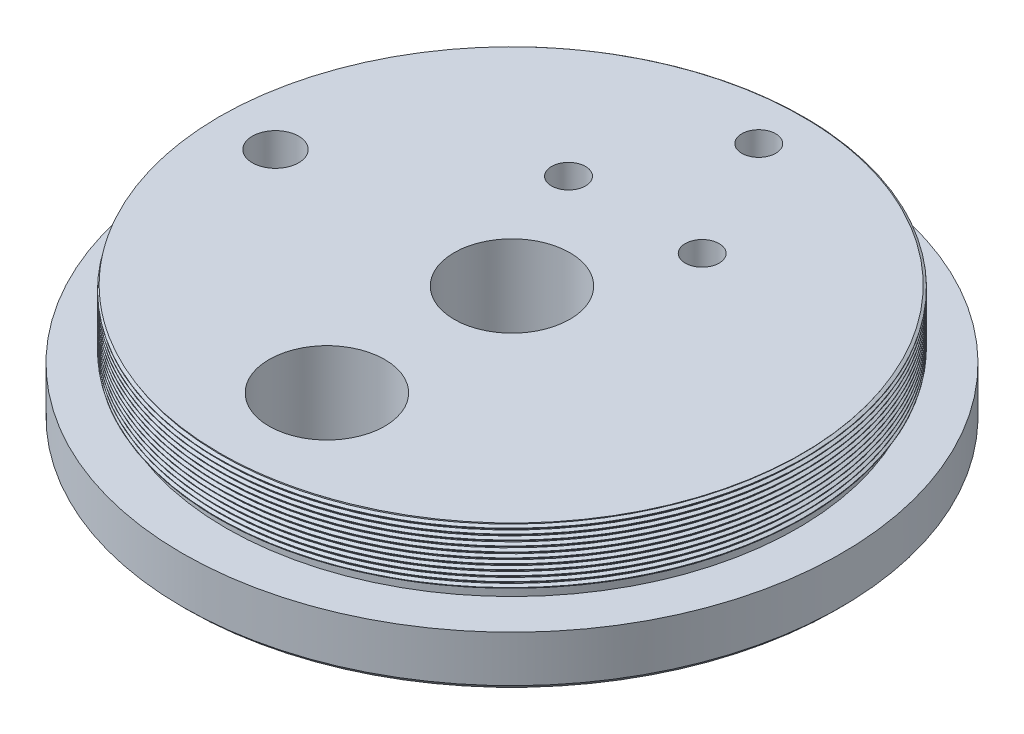
SolidWorks part; units mm, degrees
material "1060 Сплав"
ref_plane "Front Plane" through (0, 0, 0) normal (0, 0, 1) x (1, 0, 0)
ref_plane "Top Plane" through (0, 0, 0) normal (0, 1, 0) x (1, 0, 0)
ref_plane "Right Plane" through (0, 0, 0) normal (1, 0, 0) x (0, 0, -1)
sketch "Эскиз1" plane through (0, 0, 0) normal (0, 0, 1) x (1, 0, 0)
  line L0 (0, 0) -> (0, -30.3865) construction
  line L1 (-4.25, 0) -> (-32.05, 0)
  line L2 (-32.05, 0) -> (-32.05, 5)
  line L8 (-28.5, 6) -> (-28.5, 11.5)
  line L9 (-28.5, 11.5) -> (-4.25, 11.5)
  line L10 (-4.25, 11.5) -> (-4.25, 0)
  line L11 (-4.25, 0) -> (0, 0) construction
  line L12 (-32.05, 5) -> (-27.8, 5)
  line L13 (-28.5, 6) -> (-27.8, 6)
  line L14 (-27.8, 6) -> (-27.8, 5)
  dimension "D1" = 5
  dimension "D2" = 57
  dimension "D3" = 11.5
  dimension "D4" = 64.1
  dimension "D5" = 1
  dimension "D6" = 0.7
  dimension "D8" = 8.5
revolve "Повернуть1" add sketch "Эскиз1" angle 360 about L0
thread "Резьба1" pitch 1.5 method cut profile "Профиль резьбы1" start angle 0, offset 1, length 20, pitch 1.5, diameter 8.5
ref_plane "Плоскость1" through (-4.25, 12.5, 0) normal (0, 0, 1) x (-1, 0, 0)
sketch "Профиль резьбы1" plane through (-4.25, 12.5, 0) normal (0, 0, 1) x (-1, 0, 0)
  line L0 (0, 0) -> (0, 1.5) construction
  line L1 (0, 0) -> (0.8119, 0.4687)
  line L2 (0.8119, 0.4687) -> (0.8119, 0.6562)
  line L3 (0.8119, 0.6562) -> (0, 1.125)
  line L4 (0.8119, 0.5625) -> (0, 0.5625) construction
  line L11 (0, 0) -> (0, 1.125)
  point P2 (0, 0)
  dimension "Pitch" = 1.5
  dimension "Profile_Angle" = 60
  dimension "Profile_Land" = 0.1875
  dimension "Profile_Height" = 0.8119
chamfer "Фаска1" distance 0.5 angle 45 1 edges at (0, 0, 32.05)
sketch "Эскиз3" plane through (0, 0, 0) normal (0, -1, 0) x (1, 0, 0)
  line L0 (0, 0) -> (0, 18) construction
  circle A0 centre (0, 18) radius 5.625
  circle A1 centre (0, 0) radius 5.625
  dimension "D1" = 11.25
  dimension "D2" = 11.25
  dimension "D3" = 18
extrude "Вырез-Вытянуть1" cut sketch "Эскиз3" against normal through all
hole_wizard "Отверстие обработанное метчиком M41" positions "Эскиз4" profile "Эскиз5" tap size "M4" standard "ISO" end condition through all
sketch "Эскиз4" plane through (0, 0, 0) normal (0, -1, 0) x (-1, 0, 0)
  line L0 (-6.5, 12) -> (6.5, 12)
  line L2 (0, 24) -> (0, 12)
  point P0 (0, 24)
  point P2 (-6.5, 12)
  point P4 (6.5, 12)
  dimension "D1" = 24
  dimension "D2" = 13
  dimension "D3" = 12
sketch "Эскиз5" plane through (0, 0, -24) normal (1, 0, 0) x (0, 0, -1)
  line L0 (0, 0) -> (0, 11.5)
  line L1 (0, 11.5) -> (1.65, 11.5)
  line L2 (1.65, 11.5) -> (1.65, 0)
  line L5 (1.65, 0) -> (0, 0)
  line L11 (0, -6.35) -> (0, 107.95) construction
  dimension "Диаметр проходного сверла" = 3.3
  dimension "Глубина проходного сверла" = 11.5
cosmetic thread "Отверстие резьбы1"
cosmetic thread "Отверстие резьбы2"
cosmetic thread "Отверстие резьбы3"
hole_wizard "Зенковка для винта с полупотайной головкой M41" positions "Эскиз6" profile "Эскиз7" countersink size "M4" standard "ISO" end condition through all
sketch "Эскиз6" plane through (0, 0, 0) normal (0, -1, 0) x (-1, 0, 0)
  line L0 (23, 0) -> (-23, 0)
  point P0 (23, 0)
  point P10 (0, 0)
  dimension "D1" = 46
sketch "Эскиз7" plane through (-23, 0, 0) normal (1, 0, 0) x (0, 0, -1)
  line L0 (0, 0) -> (0, 11.5)
  line L1 (0, 11.5) -> (2.25, 11.5)
  line L2 (2.25, 11.5) -> (2.25, 2.45)
  line L3 (2.25, 2.45) -> (4.7, 0)
  line L5 (4.7, 0) -> (0, 0)
  line L6 (-2.25, 2.45) -> (-4.7, 0) construction
  line L11 (0, -6.35) -> (0, 107.95) construction
  dimension "Диаметр сквозного отверстия" = 4.5
  dimension "Глубина сквозного отверстия" = 11.5
  dimension "Диаметр передней зенковки" = 9.4
  dimension "Угол передней зенковки" = 90
thread "Thread1" pitch 0.5 method cut profile "Thread Profile1" start angle 0, offset 1.5, length 7, pitch 0.5, diameter 57
ref_plane "Plane1" through (-28.5, 13, 0) normal (0, 0, 1) x (-1, 0, 0)
sketch "Thread Profile1" plane through (-28.5, 13, 0) normal (0, 0, 1) x (-1, 0, 0)
  line L0 (0, 0) -> (0, 0.5) construction
  line L11 (0, 0) -> (0, 0.4375)
  line L12 (0, 0.4375) -> (-0.2706, 0.2812)
  line L13 (-0.2706, 0.2812) -> (-0.2706, 0.1562)
  line L15 (-0.2706, 0.1562) -> (0, 0)
  line L17 (-0.2706, 0.2187) -> (0, 0.2187) construction
  point P2 (0, 0)
  dimension "Pitch" = 0.5
  dimension "Profile_Angle" = 60
  dimension "Profile_Land" = 0.125
  dimension "Profile_Height" = 0.2706
